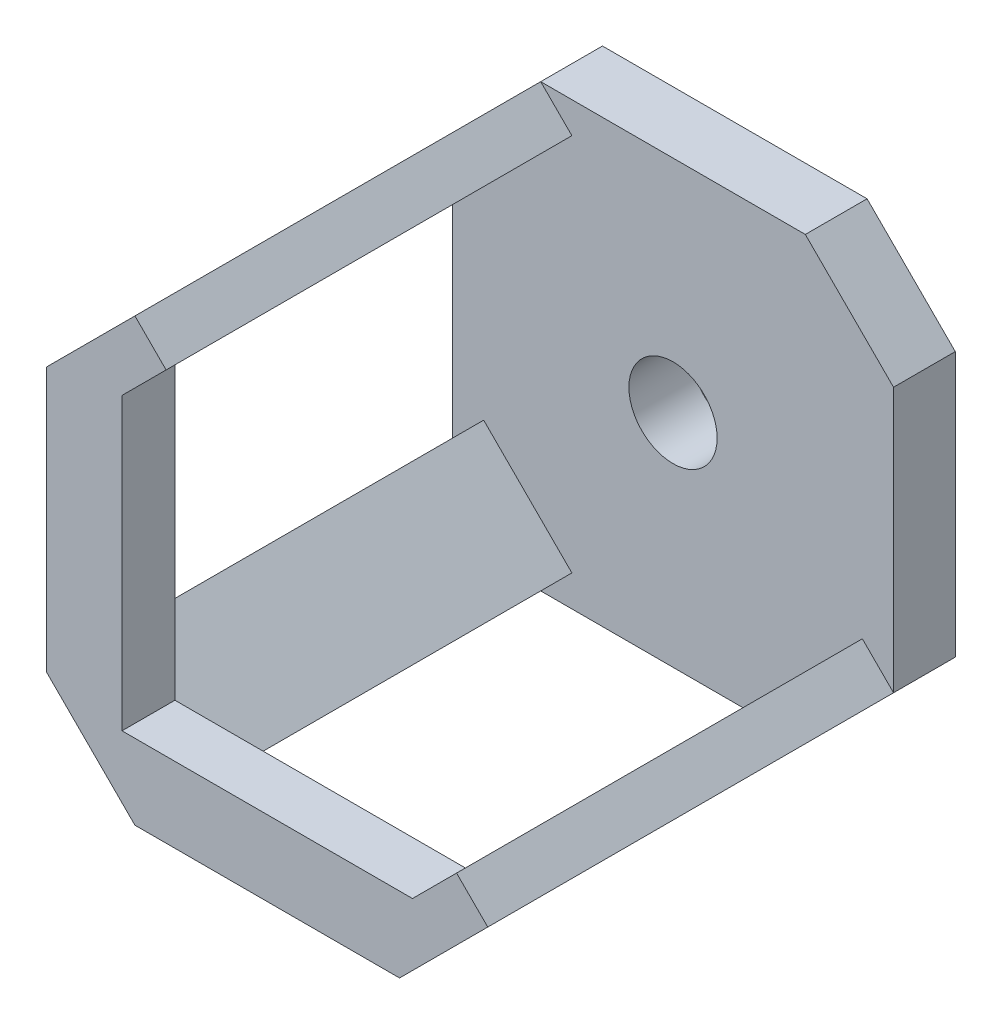
SolidWorks part; units mm, degrees
ref_plane "Plan de face" through (0, 0, 0) normal (0, 0, 1) x (1, 0, 0)
ref_plane "Plan de dessus" through (0, 0, 0) normal (0, 1, 0) x (1, 0, 0)
ref_plane "Plan de droite" through (0, 0, 0) normal (1, 0, 0) x (0, 0, -1)
sketch "Esquisse1" plane through (0, 0, 0) normal (0, 0, 1) x (1, 0, 0)
  line L1 (-26.8836, 22.9873) -> (23.1164, 22.9873)
  line L2 (-26.8836, 22.9873) -> (-26.8836, -27.0127)
  line L3 (-26.8836, -27.0127) -> (23.1164, -27.0127)
  line L4 (23.1164, 22.9873) -> (23.1164, -27.0127)
  dimension "D1" = 50
  dimension "D2" = 50
extrude "Boss.-Extru.1" add sketch "Esquisse1" along normal blind 7 contours L3 L4 L1 L2
chamfer "Chanfrein1" distance 10 angle 45 4 edges at (-26.8836, 22.9873, 3.5) (23.1164, 22.9873, 3.5) (-26.8836, -27.0127, 3.5) (23.1164, -27.0127, 3.5)
sketch "Esquisse2" plane through (0, 0, 7) normal (0, 0, 1) x (1, 0, 0)
  line L0 (-26.8836, -17.0127) -> (-16.8836, -27.0127)
  line L1 (-16.8836, -27.0127) -> (-13.348, -23.4772)
  line L2 (-13.348, -23.4772) -> (-23.348, -13.4772)
  line L3 (-23.348, -13.4772) -> (-26.8836, -17.0127)
  line L4 (-26.8836, 12.9873) -> (-16.8836, 22.9873)
  line L5 (-16.8836, 22.9873) -> (-13.348, 19.4518)
  line L6 (-13.348, 19.4518) -> (-23.348, 9.4518)
  line L7 (-23.348, 9.4518) -> (-26.8836, 12.9873)
  line L8 (23.1164, -17.0127) -> (19.5809, -13.4772)
  line L9 (19.5809, -13.4772) -> (9.5809, -23.4772)
  line L10 (9.5809, -23.4772) -> (13.1164, -27.0127)
  line L11 (-16.8836, -27.0127) -> (13.1164, -27.0127) construction
  line L12 (13.1164, -27.0127) -> (23.1164, -17.0127) construction
  line L13 (13.1164, -27.0127) -> (23.1164, -17.0127)
  line M8 (-16.8836, 22.9873) -> (-26.8836, 12.9873)
  line M12 (13.1164, -27.0127) -> (23.1164, -17.0127)
  dimension "D1" = 5
  dimension "D2" = 5
  dimension "D3" = 5
  dimension "D4" = 5
  dimension "D5" = 5
  dimension "D6" = 5
extrude "Boss.-Extru.2" add sketch "Esquisse2" along normal blind 40 contours L7 L6 L5 M8 | L9 L10 L8 M12 | L2 L3 L0 L1 region at (-20.1158, 16.2195, 7) region at (16.3487, -20.2449, 7)
ref_plane "Plan1" through (0, 0, 47) normal (0, 0, 1) x (1, 0, 0)
sketch "Esquisse4" plane through (0, 0, 47) normal (0, 0, 1) x (1, 0, 0)
  line L0 (-18.348, 14.4518) -> (-13.348, 19.4518)
  line L1 (-13.348, 19.4518) -> (-23.348, 9.4518) construction
  line L2 (-13.348, 19.4518) -> (-16.8836, 22.9873)
  line L3 (-16.8836, 22.9873) -> (-26.8836, 12.9873)
  line L4 (-26.8836, 12.9873) -> (-26.8836, -17.0127)
  line L5 (-26.8836, -17.0127) -> (-16.8836, -27.0127)
  line L6 (-16.8836, -27.0127) -> (13.1164, -27.0127)
  line L7 (13.1164, -27.0127) -> (23.1164, -17.0127)
  line L8 (23.1164, -17.0127) -> (19.5809, -13.4772)
  line L9 (19.5809, -13.4772) -> (14.5809, -18.4772)
  line L10 (19.5809, -13.4772) -> (9.5809, -23.4772) construction
  line L11 (14.5809, -18.4772) -> (-18.348, -18.4772)
  line L12 (-13.348, -23.4772) -> (-23.348, -13.4772) construction
  line L13 (-18.348, -18.4772) -> (-18.348, 14.4518)
extrude "Boss.-Extru.3" add sketch "Esquisse4" along normal blind 6
sketch "Esquisse5" plane through (0, 0, 0) normal (0, 0, -1) x (-1, 0, 0)
  line L0 (-23.1164, 12.9873) -> (-23.1164, -17.0127) construction
  line L1 (16.8836, 22.9873) -> (-13.1164, 22.9873) construction
  circle A0 centre (1.8836, -2.0127) radius 5
  point P2 (-23.1164, -2.0127)
  dimension "D3" = 10
  dimension "D1" = 25
  dimension "D2" = 25
extrude "Enlèv. mat.-Extru.1" cut sketch "Esquisse5" against normal up to surface (7 mm away) contours A0 up to face at (-4.2356, -4.3648, 7)
